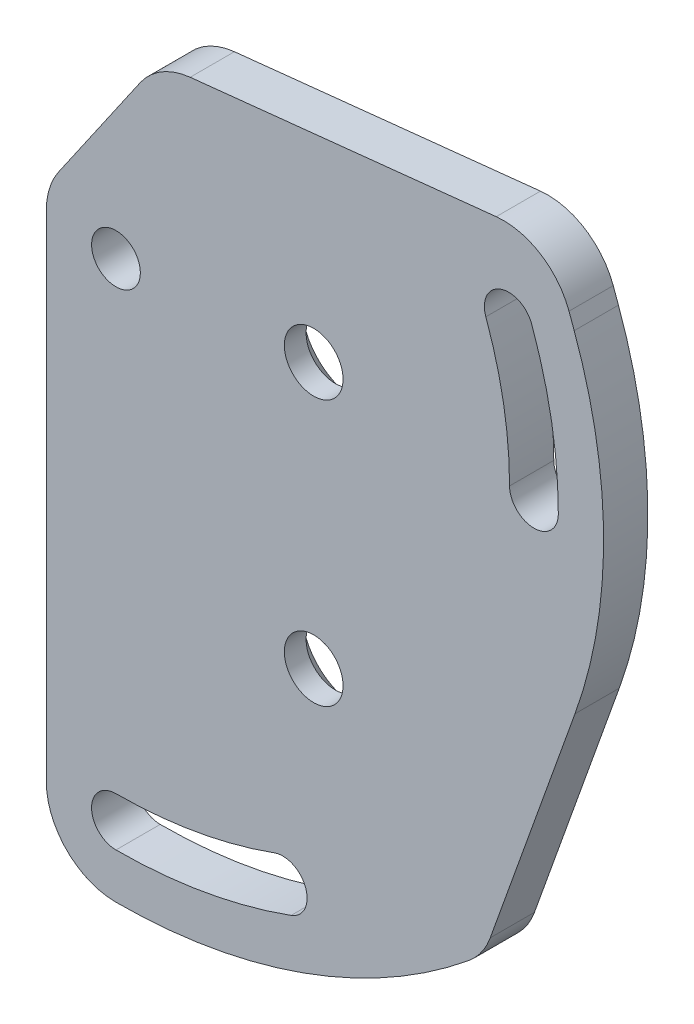
SolidWorks part; units mm, degrees
material "7075-T6, Plate (SS)"
ref_plane "Front Plane" through (0, 0, 0) normal (0, 0, 1) x (1, 0, 0)
ref_plane "Top Plane" through (0, 0, 0) normal (0, 1, 0) x (1, 0, 0)
ref_plane "Right Plane" through (0, 0, 0) normal (1, 0, 0) x (0, 0, -1)
sketch "Sketch3" plane through (0, 0, 0) normal (0, 0, 1) x (1, 0, 0)
  line L0 (0, 0) -> (0, 70) construction
  line L1 (0, 70) -> (23.9414, 4.2215) construction
  line L2 (23.9414, 4.2215) -> (80.323, 24.7427) construction
  line L3 (80.323, 24.7427) -> (56.3816, 90.5212) construction
  line L4 (56.3816, 90.5212) -> (0, 70) construction
  arc A0 (56.3816, 90.5212) -> (60, 70) centre (0, 70) cw construction
  arc A1 (80.323, 24.7427) -> (60, 0) centre (0, 70) cw construction
  arc A2 (23.9414, 4.2215) -> (0, 0) centre (0, 70) cw construction
  arc A3 (53.0926, 89.3241) -> (56.5, 70) centre (0, 70) cw
  arc A4 (77.2737, 26.4608) -> (57.7222, 2.6574) centre (0, 70) cw
  arc A5 (22.7443, 7.5104) -> (0, 3.5) centre (0, 70) cw
  arc A6 (59.6705, 91.7183) -> (63.5, 70) centre (0, 70) cw
  arc A7 (83.3723, 23.0246) -> (62.2778, -2.6574) centre (0, 70) cw
  arc A8 (25.1385, 0.9326) -> (0, -3.5) centre (0, 70) cw
  arc A9 (53.0926, 89.3241) -> (59.6705, 91.7183) centre (56.3816, 90.5212) cw
  arc A10 (56.5, 70) -> (63.5, 70) centre (60, 70) ccw
  arc A11 (77.2737, 26.4608) -> (83.3723, 23.0246) centre (80.323, 24.7427) cw
  arc A12 (57.7222, 2.6574) -> (62.2778, -2.6574) centre (60, 0) ccw
  arc A13 (22.7443, 7.5104) -> (25.1385, 0.9326) centre (23.9414, 4.2215) cw
  arc A14 (0, 3.5) -> (0, -3.5) centre (0, 0) ccw
  circle A15 centre (0, 70) radius 3.5
  dimension "D4" = 3.5
  dimension "D6" = 7
  dimension "D1" = 70
  dimension "D2" = 60
  dimension "D3" = 20
  dimension "D5" = 3.5
sketch "Sketch2" plane through (0, 0, 0) normal (0, 0, 1) x (1, 0, 0)
  line L0 (-10, -10) -> (-10, 103.3383)
  line L1 (-10, 103.3383) -> (62.3583, 103.3383)
  line L2 (62.3583, 103.3383) -> (91.2444, 23.9743)
  line L3 (63.5917, -10) -> (-10, -10)
  line L5 (0, 0) -> (0, 70) construction
  line L7 (80.323, 24.7427) -> (56.3816, 90.5212) construction
  line L9 (56.3816, 90.5212) -> (0, 70) construction
  arc A0 (91.2444, 23.9743) -> (63.5917, -10) centre (0, 70) cw
  arc A1 (60, 0) -> (80.323, 24.7427) centre (0, 70) ccw construction
  dimension "D5" = 10
  dimension "D1" = 10
  dimension "D2" = 10
  dimension "D3" = 10
  dimension "D4" = 10
extrude "Boss-Extrude1" add sketch "Sketch2" along normal blind 6.35
extrude "Cut-Extrude2" cut sketch "Sketch3" along normal through all
sketch "Sketch4" plane through (0, 0, 0) normal (0, 0, 1) x (1, 0, 0)
  line L0 (91.2444, 23.9743) -> (62.3583, 103.3383) construction
  line L1 (65.893, 46.3756) -> (52.822, 9.9181)
  line L2 (-10, -10) -> (63.5917, -10) construction
  line L3 (-10, 74.1115) -> (6.0845, 97.4001)
  line L4 (28.385, 71.3157) -> (28.385, 33.2157) construction
  line L5 (9.335, 90.3657) -> (47.435, 90.3657) construction
  line L6 (9.335, 90.3657) -> (9.335, 14.1657) construction
  line L8 (-10, 103.3383) -> (-10, -10) construction
  line L9 (65.7785, 93.9414) -> (62.3583, 103.3383)
  line L10 (62.3583, 103.3383) -> (6.0845, 97.4001)
  line L11 (-10, 74.1115) -> (-10, -10)
  line L12 (-10, -10) -> (0, -10)
  line L13 (9.335, 14.1657) -> (47.435, 14.1657) construction
  line L14 (47.435, 90.3657) -> (47.435, 14.1657) construction
  arc A0 (65.7785, 93.9414) -> (65.893, 46.3756) centre (0, 70) cw
  arc A6 (56.5, 70) -> (63.5, 70) centre (60, 70) ccw construction
  arc A7 (0, -10) -> (52.822, 9.9181) centre (0, 70) ccw
  arc A8 (0, -10) -> (52.822, 9.9181) centre (0, 70) ccw
  point P19 (28.385, 90.3657)
  point P20 (9.335, 52.2657)
  point P29 (28.385, 52.2657)
  dimension "D1" = 10
  dimension "D2" = 76.2
  dimension "D3" = 38.1
extrude "Cut-Extrude3" cut sketch "Sketch4" along normal through all flip side to cut contours L12 A7 L1 A0 L9 L10 L11
fillet "Fillet1" radius 10 5 edges at (52.822, 9.9181, 3.175) (-10, -10, 3.175) (-10, 74.1115, 3.175) (62.3583, 103.3383, 3.175) (6.0845, 97.4001, 3.175)
hole_wizard "CSK for 5/16 Flat Head Machine Screw (100)2" [suppressed] positions "Sketch6" profile "Sketch7" countersink size "5/16" standard "ANSI Inch"
sketch "Sketch6" plane through (0, 0, 6.35) normal (0, 0, 1) x (1, 0, 0)
  point P0 (28.385, 71.3157)
  point P3 (28.385, 33.2157)
sketch "Sketch7" plane through (28.385, 71.3157, 6.35) normal (1, 0, 0) x (0, -1, 0)
  line L0 (0, 0) -> (0, 6.35)
  line L1 (0, 6.35) -> (4.2164, 6.35)
  line L2 (4.2164, 6.35) -> (4.2164, 3.2289)
  line L3 (4.2164, 3.2289) -> (8.0645, 0)
  line L5 (8.0645, 0) -> (0, 0)
  line L6 (-4.2164, 3.2289) -> (-8.0645, 0) construction
  line L11 (0, -6.35) -> (0, 107.95) construction
  dimension "Thru Hole Dia." = 8.4328
  dimension "Thru Hole Depth" = 6.35
  dimension "Near C'Sink Dia." = 16.129
  dimension "Near C'Sink Angle" = 100
hole_wizard "CSK for 5/16 Flat Head Machine Screw (100)1" positions "Sketch8" profile "Sketch9" countersink size "5/16" standard "ANSI Inch" end condition through all
sketch "Sketch8" plane through (0, 0, 0) normal (0, 0, -1) x (-1, 0, 0)
  point P0 (-28.385, 71.3157)
  point P3 (-28.385, 33.2157)
sketch "Sketch9" plane through (28.385, 71.3157, 0) normal (1, 0, 0) x (0, 1, 0)
  line L0 (0, 0) -> (0, 6.35)
  line L1 (0, 6.35) -> (4.2164, 6.35)
  line L2 (4.2164, 6.35) -> (4.2164, 3.2289)
  line L3 (4.2164, 3.2289) -> (8.0645, 0)
  line L5 (8.0645, 0) -> (0, 0)
  line L6 (-4.2164, 3.2289) -> (-8.0645, 0) construction
  line L11 (0, -6.35) -> (0, 107.95) construction
  dimension "Thru Hole Dia." = 8.4328
  dimension "Thru Hole Depth" = 6.35
  dimension "Near C'Sink Dia." = 16.129
  dimension "Near C'Sink Angle" = 100
